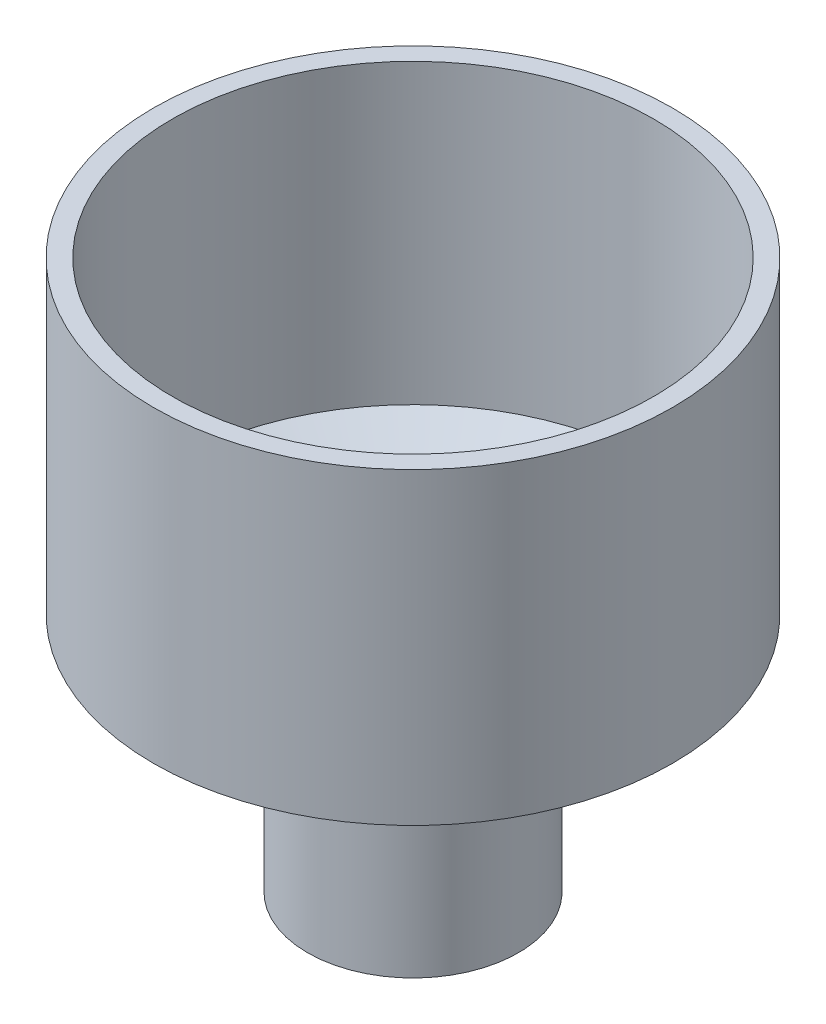
SolidWorks part; units mm, degrees
ref_plane "Front Plane" through (0, 0, 0) normal (0, 0, 1) x (1, 0, 0)
ref_plane "Top Plane" through (0, 0, 0) normal (0, 1, 0) x (1, 0, 0)
ref_plane "Right Plane" through (0, 0, 0) normal (1, 0, 0) x (0, 0, -1)
sketch "Sketch2" plane through (0, 0, 0) normal (0, 0, 1) x (1, 0, 0)
  line L0 (0, 0) -> (0, 101.6) construction
  line L1 (0, 0) -> (16, 0)
  line L2 (16, 0) -> (16, 30)
  line L3 (16, 30) -> (44.5, 46.6)
  line L4 (44.5, 46.6) -> (44.5, 101.6)
  line L5 (44.5, 101.6) -> (0, 101.6)
  line L6 (0, -3.5) -> (19.5, -3.5)
  line L7 (19.5, -3.5) -> (19.5, 27.9882)
  line L8 (19.5, 27.9882) -> (48, 44.5882)
  line L9 (48, 44.5882) -> (48, 105.1)
  line L10 (48, 105.1) -> (0, 105.1)
  line L11 (16, 0) -> (19.5, 0)
  line L12 (44.5, 101.6) -> (48, 101.6)
  dimension "D1" = 101.6
  dimension "D2" = 44.5
  dimension "D3" = 16
  dimension "D4" = 30
  dimension "D5" = 55
  dimension "D6" = 3.5
revolve "Revolve1" add sketch "Sketch2" angle 360 about L0 region at (17.0652, 15, 0)
sketch "Sketch3" plane through (0, 0, 0) normal (0, 0, 1) x (1, 0, 0)
  line L0 (0, 0) -> (0, 55.3784) construction
  line L1 (-19.5, 0) -> (19.5, 0) construction
  circle A0 centre (0, 25.25) radius 3.25
  circle A1 centre (0, 5.25) radius 3.25
  dimension "D1" = 20
  dimension "D2" = 5.25
extrude "Cut-Extrude1" [suppressed] cut sketch "Sketch3" against normal blind 50 and the other way blind 50
